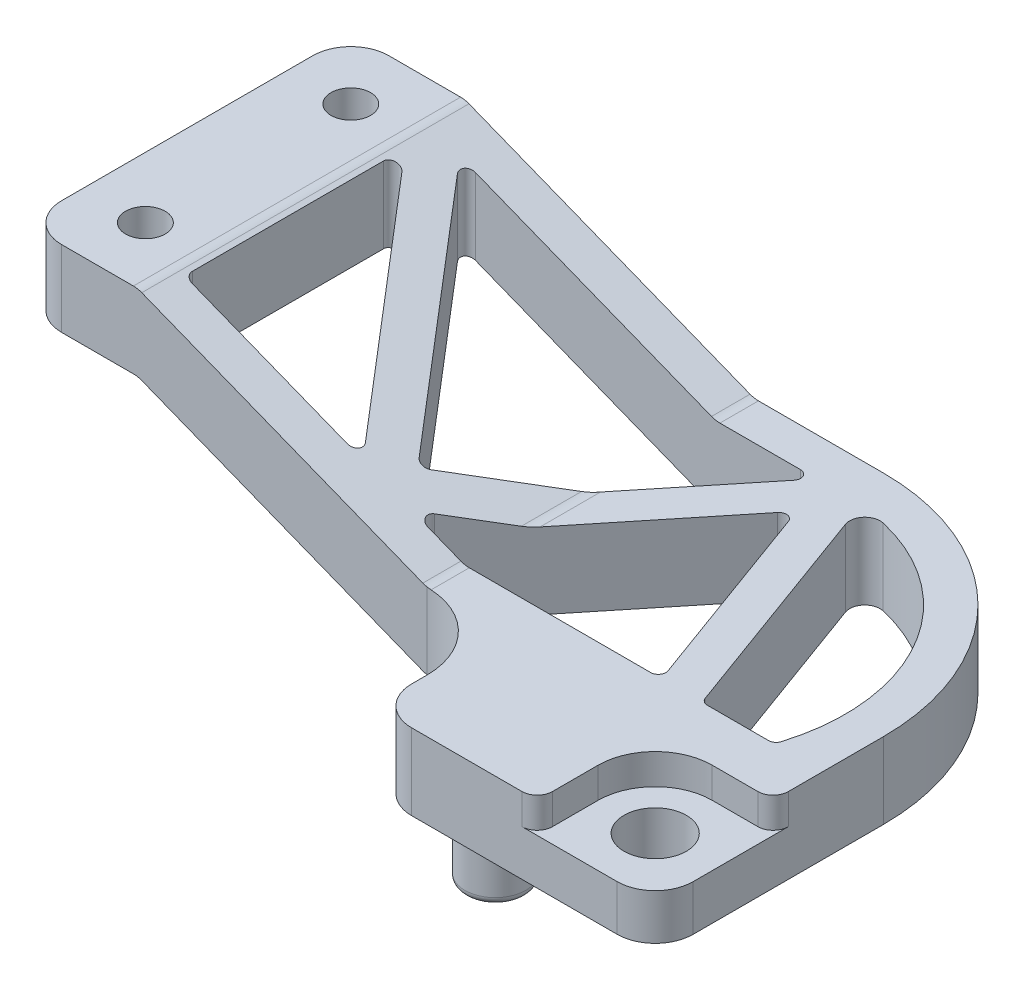
SolidWorks part; units mm, degrees
ref_plane "Front Plane" through (0, 0, 0) normal (0, 0, 1) x (1, 0, 0)
ref_plane "Top Plane" through (0, 0, 0) normal (0, 1, 0) x (1, 0, 0)
ref_plane "Right Plane" through (0, 0, 0) normal (1, 0, 0) x (0, 0, -1)
sketch "Sketch1" plane through (0, 0, 0) normal (0, 1, 0) x (1, 0, 0)
  line L0 (-15.9009, 67.2516) -> (-15.9009, 34.3134) construction
  line L1 (11.2739, 72.3134) -> (4.7921, 72.3134)
  line L2 (41.2739, 42.3134) -> (41.2739, 17.3134)
  line L3 (36.2739, 12.3134) -> (9.2739, 12.3134)
  line L4 (4.2739, 19.3134) -> (4.2739, 17.3134)
  line L5 (4.7921, 72.3134) -> (-53.7261, 72.3134)
  line L7 (-5.7261, 29.3134) -> (-53.7261, 29.3134)
  line L8 (-58.7261, 67.3134) -> (-58.7261, 34.3134)
  line L9 (34.1714, 34.3134) -> (26.1348, 34.3134)
  line L10 (-42.5577, 35.3134) -> (-42.5577, 60.4524)
  line L11 (-37.2458, 67.2516) -> (5.4439, 67.2516)
  line L12 (-42.5577, 67.2516) -> (-15.9009, 34.3134) construction
  line L13 (10.7558, 67.2516) -> (22.7739, 34.3134) construction
  line L14 (-15.9009, 34.3134) -> (10.7558, 67.2516) construction
  line L15 (-40.7803, 61.0815) -> (-20.4355, 35.9425)
  line L16 (-38.0231, 65.6225) -> (-16.6783, 39.2479)
  line L18 (6.2213, 65.6225) -> (-15.1236, 39.2479)
  line L19 (-21.2128, 34.3134) -> (-41.5577, 34.3134)
  line L20 (25.1954, 34.9706) -> (14.6158, 63.9661)
  line L21 (19.6228, 35.6562) -> (10.5265, 60.5866)
  line L22 (8.8097, 60.8729) -> (-11.3664, 35.9425)
  line L23 (18.6834, 34.3134) -> (-10.589, 34.3134)
  circle A0 centre (33.2739, 20.3134) radius 4.1
  circle A1 centre (12.2739, 20.3134) radius 4
  circle A2 centre (-50.7261, 64.3134) radius 2.6
  circle A3 centre (-50.7261, 37.3134) radius 2.6
  arc A4 (4.2739, 19.3134) -> (-5.7261, 29.3134) centre (-5.7261, 19.3134) ccw
  arc A5 (11.2739, 72.3134) -> (41.2739, 42.3134) centre (11.2739, 42.3134) cw
  arc A6 (41.2739, 17.3134) -> (36.2739, 12.3134) centre (36.2739, 17.3134) cw
  arc A7 (9.2739, 12.3134) -> (4.2739, 17.3134) centre (9.2739, 17.3134) cw
  arc A8 (-53.7261, 72.3134) -> (-58.7261, 67.3134) centre (-53.7261, 67.3134) ccw
  arc A9 (-53.7261, 29.3134) -> (-58.7261, 34.3134) centre (-53.7261, 34.3134) cw
  arc A12 (-20.4355, 35.9425) -> (-21.2128, 34.3134) centre (-21.2128, 35.3134) cw
  arc A13 (35.1277, 35.0211) -> (16.9525, 66.602) centre (11.2739, 42.3134) ccw
  arc A14 (-41.5577, 34.3134) -> (-42.5577, 35.3134) centre (-41.5577, 35.3134) cw
  arc A15 (-40.7803, 61.0815) -> (-42.5577, 60.4524) centre (-41.5577, 60.4524) ccw
  arc A16 (-16.6783, 39.2479) -> (-15.1236, 39.2479) centre (-15.9009, 39.877) ccw
  arc A17 (6.2213, 65.6225) -> (5.4439, 67.2516) centre (5.4439, 66.2516) ccw
  arc A18 (-38.0231, 65.6225) -> (-37.2458, 67.2516) centre (-37.2458, 66.2516) cw
  arc A19 (35.1277, 35.0211) -> (34.1714, 34.3134) centre (34.1714, 35.3134) cw
  arc A20 (25.1954, 34.9706) -> (26.1348, 34.3134) centre (26.1348, 35.3134) ccw
  arc A21 (19.6228, 35.6562) -> (18.6834, 34.3134) centre (18.6834, 35.3134) cw
  arc A22 (10.5265, 60.5866) -> (8.8097, 60.8729) centre (9.587, 60.2438) ccw
  arc A23 (-10.589, 34.3134) -> (-11.3664, 35.9425) centre (-10.589, 35.3134) cw
  arc A24 (16.9525, 66.602) -> (14.6158, 63.9661) centre (16.4967, 64.6524) ccw
  point P47 (-19.1171, 34.3134)
  point P54 (-15.9009, 38.2874)
  point P65 (20.1127, 34.3134)
  point P68 (9.921, 62.246)
  dimension "D1" = 21
  dimension "D9" = 27
  dimension "D13" = 10
  dimension "D14" = 30
  dimension "D15" = 5
  dimension "D16" = 2.5
  dimension "D21" = 1
  dimension "D22" = 1
  dimension "D23" = 1
  dimension "D19" = 8.2
  dimension "D24" = 8
  dimension "D25" = 5.2
  dimension "D26" = 5.2
  dimension "D2" = 8
  dimension "D3" = 8
  dimension "D4" = 8
  dimension "D5" = 8
  dimension "D6" = 60
  dimension "D7" = 100
  dimension "D8" = 43
  dimension "D10" = 8
  dimension "D11" = 8
  dimension "D12" = 8
  dimension "D17" = 2.5
  dimension "D18" = 2.5
  dimension "D20" = 2.5
extrude "Boss-Extrude1" add sketch "Sketch1" along normal blind 10
sketch "Sketch2" plane through (0, 10, 0) normal (0, 1, 0) x (1, 0, 0)
  line L0 (33.2739, 27.8134) -> (41.2739, 27.8134)
  line L1 (41.2739, 17.3134) -> (41.2739, 42.3134) construction
  line L2 (41.2739, 27.8134) -> (41.2739, 17.3134)
  line L3 (25.7739, 20.3134) -> (25.7739, 12.3134)
  line L4 (9.2739, 12.3134) -> (36.2739, 12.3134) construction
  line L5 (25.7739, 12.3134) -> (36.2739, 12.3134)
  arc A0 (33.2739, 27.8134) -> (25.7739, 20.3134) centre (33.2739, 20.3134) ccw
  arc A1 (36.2739, 12.3134) -> (41.2739, 17.3134) centre (36.2739, 17.3134) ccw
extrude "Cut-Extrude1" cut sketch "Sketch2" against normal blind 4
fillet "Fillet1" radius 2 2 edges at (41.2739, 8, -27.8134) (25.7739, 8, -12.3134)
sketch "Sketch3" plane through (0, 10, 0) normal (0, 1, 0) x (1, 0, 0)
  circle A0 centre (12.2739, 20.3134) radius 4
  circle A1 centre (12.2739, 20.3134) radius 4 construction
extrude "Boss-Extrude2" add sketch "Sketch3" against normal blind 20
fillet "Fillet2" radius 1 2 edges at (12.2739, -10, -16.3134) (12.2739, 0, -16.3134)
sketch "Sketch4" plane through (0, 10, 0) normal (0, 1, 0) x (1, 0, 0)
  line L0 (-58.7261, 67.3134) -> (-58.7261, 34.3134)
  line L1 (-5.7261, 29.3134) -> (-53.7261, 29.3134)
  line L2 (-5.7261, 29.3134) -> (-5.7261, 34.3134)
  line L3 (-5.7261, 72.3134) -> (-53.7261, 72.3134)
  line L5 (-16.6783, 39.2479) -> (-38.0231, 65.6225)
  line L6 (-37.2458, 67.2516) -> (-5.7261, 67.2516)
  line L7 (5.4439, 67.2516) -> (-37.2458, 67.2516) construction
  line L8 (-15.1236, 39.2479) -> (-5.7261, 50.8134)
  line L9 (-5.7261, 67.2516) -> (-5.7261, 72.3134)
  line L10 (-40.7803, 61.0815) -> (-20.4355, 35.9425)
  line L11 (-42.5577, 60.4524) -> (-42.5577, 35.3134)
  line L12 (-41.5577, 34.3134) -> (-21.2128, 34.3134)
  line L13 (-11.3664, 35.9425) -> (-5.7261, 42.9119)
  line L14 (8.8097, 60.8729) -> (-11.3664, 35.9425) construction
  line L15 (-10.589, 34.3134) -> (-5.7261, 34.3134)
  line L16 (-10.589, 34.3134) -> (18.6834, 34.3134) construction
  line L17 (-5.7261, 42.9119) -> (-5.7261, 50.8134)
  arc A0 (-53.7261, 72.3134) -> (-58.7261, 67.3134) centre (-53.7261, 67.3134) ccw
  arc A1 (-58.7261, 34.3134) -> (-53.7261, 29.3134) centre (-53.7261, 34.3134) ccw
  circle A2 centre (-50.7261, 64.3134) radius 2.6
  circle A3 centre (-50.7261, 37.3134) radius 2.6
  arc A4 (-40.7803, 61.0815) -> (-42.5577, 60.4524) centre (-41.5577, 60.4524) ccw
  arc A5 (-42.5577, 35.3134) -> (-41.5577, 34.3134) centre (-41.5577, 35.3134) ccw
  arc A6 (-21.2128, 34.3134) -> (-20.4355, 35.9425) centre (-21.2128, 35.3134) ccw
  arc A7 (-16.6783, 39.2479) -> (-15.1236, 39.2479) centre (-15.9009, 39.877) ccw
  arc A8 (-37.2458, 67.2516) -> (-38.0231, 65.6225) centre (-37.2458, 66.2516) ccw
  arc A9 (-11.3664, 35.9425) -> (-10.589, 34.3134) centre (-10.589, 35.3134) ccw
extrude "Boss-Extrude3" add sketch "Sketch4" along normal blind 15
sketch "Sketch5" plane through (0, 0, -29.3134) normal (0, 0, 1) x (1, 0, 0)
  line L0 (-5.7261, 10) -> (-43.7261, 25)
  line L1 (-53.7261, 25) -> (-5.7261, 25) construction
  line L2 (-43.7261, 25) -> (-5.7261, 25)
  line L3 (-5.7261, 25) -> (-5.7261, 10)
  line L4 (-53.7261, 25) -> (-53.7261, 0) construction
  line L5 (-53.7261, 15) -> (-43.7261, 15)
  line L6 (-43.7261, 15) -> (-5.7261, 0)
  line L7 (-53.7261, 15) -> (-60.9453, 15)
  line L8 (-60.9453, 15) -> (-60.9453, 0)
  line L9 (-60.9453, 0) -> (-5.7261, 0)
  dimension "D1" = 10
  dimension "D2" = 10
extrude "Cut-Extrude2" cut sketch "Sketch5" against normal up to next
fillet "Fillet3" radius 3 8 edges at (-5.7261, 10, -31.8134) (-5.7261, 10, -46.8627) (-5.7261, 10, -69.7825) (-43.7261, 25, -50.8134) (-5.7261, 0, -69.7825) (-5.7261, 0, -46.8859) (-5.7261, 0, -31.8134) (-43.7261, 15, -50.8134)
sketch "Sketch6" plane through (0, 15, 0) normal (0, -1, 0) x (-1, 0, 0)
  line L1 (54.8004, 61.9024) -> (54.8512, 66.6364)
  line L2 (54.8512, 66.6364) -> (50.7769, 69.0474)
  line L3 (50.7769, 69.0474) -> (46.6517, 66.7245)
  line L4 (46.6517, 66.7245) -> (46.6009, 61.9905)
  line L5 (46.6009, 61.9905) -> (50.6752, 59.5794)
  line L6 (50.6752, 59.5794) -> (54.8004, 61.9024)
  line L7 (54.801, 39.6661) -> (50.726, 42.0188)
  line L8 (50.726, 42.0188) -> (46.651, 39.6661)
  line L9 (46.651, 39.6661) -> (46.6511, 34.9607)
  line L10 (46.6511, 34.9607) -> (50.7261, 32.608)
  line L11 (50.7261, 32.608) -> (54.8011, 34.9607)
  line L12 (54.8011, 34.9607) -> (54.801, 39.6661)
  circle A0 centre (50.7261, 64.3134) radius 4.1 construction
  circle A1 centre (50.7261, 37.3134) radius 4.075 construction
extrude "Cut-Extrude3" cut sketch "Sketch6" against normal blind 6
